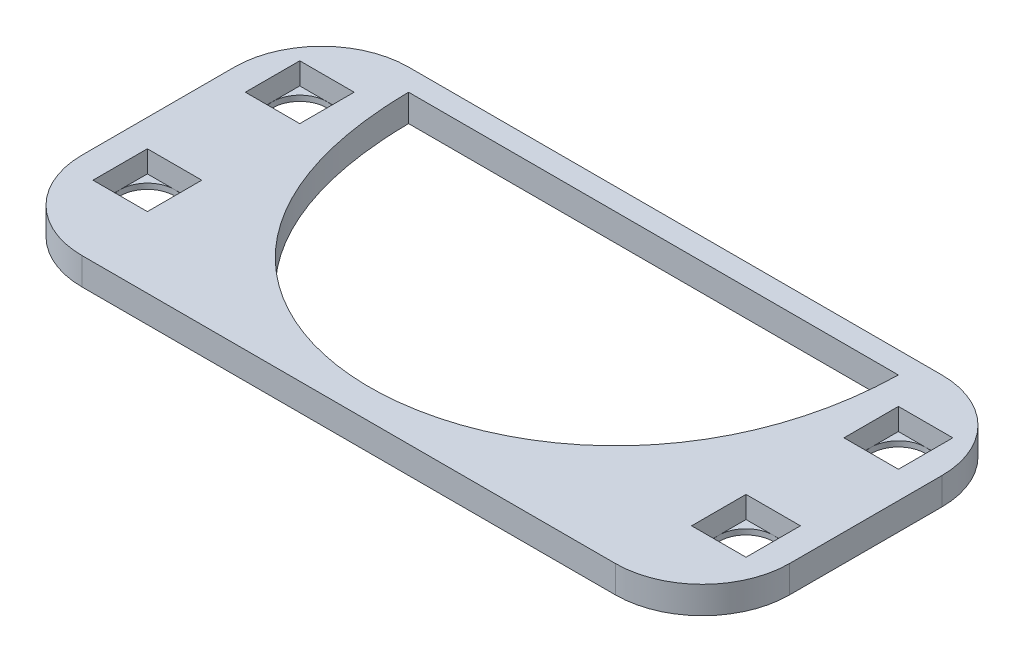
SolidWorks part; units mm, degrees
ref_plane "Front Plane" through (0, 0, 0) normal (0, 0, 1) x (1, 0, 0)
ref_plane "Top Plane" through (0, 0, 0) normal (0, 1, 0) x (1, 0, 0)
ref_plane "Right Plane" through (0, 0, 0) normal (1, 0, 0) x (0, 0, -1)
sketch "Sketch1" plane through (0, 0, 0) normal (0, 1, 0) x (1, 0, 0)
  line L1 (0, 0) -> (65, 0)
  line L2 (0, 0) -> (0, 30)
  line L3 (0, 30) -> (65, 30)
  line L4 (65, 0) -> (65, 30)
  dimension "D1" = 65
  dimension "D2" = 30
extrude "Boss-Extrude1" add sketch "Sketch1" along normal blind 2.5
sketch "Sketch2" plane through (0, 2.5, 0) normal (0, 1, 0) x (1, 0, 0)
  line L0 (10, 28) -> (55, 28)
  line L1 (0, 30) -> (0, 0) construction
  line L2 (65, 30) -> (0, 30) construction
  line L3 (65, 0) -> (65, 30) construction
  line L5 (7.5, 25.5) -> (2.5, 25.5)
  line L6 (7.5, 25.5) -> (7.5, 20.5)
  line L7 (7.5, 20.5) -> (2.5, 20.5)
  line L8 (2.5, 25.5) -> (2.5, 20.5)
  line L9 (7.5, 25.5) -> (2.5, 20.5) construction
  line L10 (7.5, 20.5) -> (2.5, 25.5) construction
  line L11 (7.5, 11.5) -> (2.5, 11.5)
  line L12 (7.5, 11.5) -> (7.5, 6.5)
  line L13 (7.5, 6.5) -> (2.5, 6.5)
  line L14 (2.5, 11.5) -> (2.5, 6.5)
  line L15 (7.5, 11.5) -> (2.5, 6.5) construction
  line L16 (7.5, 6.5) -> (2.5, 11.5) construction
  line L17 (57.5, 11.5) -> (62.5, 11.5)
  line L18 (57.5, 11.5) -> (57.5, 6.5)
  line L19 (57.5, 6.5) -> (62.5, 6.5)
  line L20 (62.5, 11.5) -> (62.5, 6.5)
  line L21 (57.5, 11.5) -> (62.5, 6.5) construction
  line L22 (57.5, 6.5) -> (62.5, 11.5) construction
  line L23 (57.5, 25.5) -> (62.5, 25.5)
  line L24 (57.5, 25.5) -> (57.5, 20.5)
  line L25 (57.5, 20.5) -> (62.5, 20.5)
  line L26 (62.5, 25.5) -> (62.5, 20.5)
  line L27 (57.5, 25.5) -> (62.5, 20.5) construction
  line L28 (57.5, 20.5) -> (62.5, 25.5) construction
  circle A0 centre (5, 23) radius 2.5
  circle A1 centre (5, 9) radius 2.5
  circle A2 centre (60, 23) radius 2.5
  circle A3 centre (60, 9) radius 2.5
  spline S0 degree 3 poles (55, 28) (54.2636, -4.3321) (10.3361, -7.0196) (10, 28) knots 0 0 0 0 1 1 1 1
  point P34 (21.4129, 10.0067)
  point P35 (43.809, 10.5593)
  dimension "D3" = 2
  dimension "D5" = 5
  dimension "D6" = 5
  dimension "D7" = 5
  dimension "D8" = 5
  dimension "D1" = 45
  dimension "D2" = 10
  dimension "D4" = 14
  dimension "D9" = 5
  dimension "D10" = 5
  dimension "D11" = 7
  dimension "D12" = 5
  dimension "D13" = 5
  dimension "D14" = 5
  dimension "D15" = 5
  dimension "D16" = 5
  dimension "D17" = 5
  dimension "D18" = 5
  dimension "D19" = 5
extrude "Cut-Extrude1" cut sketch "Sketch2" against normal through all contours A0 | A1 | A3 | A2 | S0 L0
extrude "Cut-Extrude2" cut sketch "Sketch2<3>" against normal blind 2 contours A1 L13 L12 | A1 L12 L11 | A1 L11 L14 | A1 L14 L13 | A0 L5 L8 | A0 L6 L5 | A0 L7 L6 | A0 L8 L7 | A2 L23 L24 | A2 L26 L23 | A2 L25 L26 | A2 L24 L25 | A3 L19 L20 | A3 L18 L19 | A3 L17 L18 | A3 L20 L17 region at (6.9416, 2.5, -24.9416) region at (3.0584, 2.5, -24.9416) region at (6.9416, 2.5, -21.0584) region at (3.0584, 2.5, -21.0584) region at (6.9416, 2.5, -10.9416) region at (3.0584, 2.5, -10.9416) region at (6.9416, 2.5, -7.0584) region at (3.0584, 2.5, -7.0584) region at (58.0584, 2.5, -10.9416) region at (61.9416, 2.5, -10.9416) region at (58.0584, 2.5, -7.0584) region at (61.9416, 2.5, -7.0584) region at (58.0584, 2.5, -24.9416) region at (61.9416, 2.5, -24.9416) region at (58.0584, 2.5, -21.0584) region at (61.9416, 2.5, -21.0584)
sketch "Sketch2<3>" plane through (0, 2.5, 0) normal (0, 1, 0) x (1, 0, 0) same geometry as "Sketch2"
fillet "Fillet1" radius 8 4 edges at (65, 1.25, 0) (65, 1.25, -30) (0, 1.25, -30) (0, 1.25, 0)
